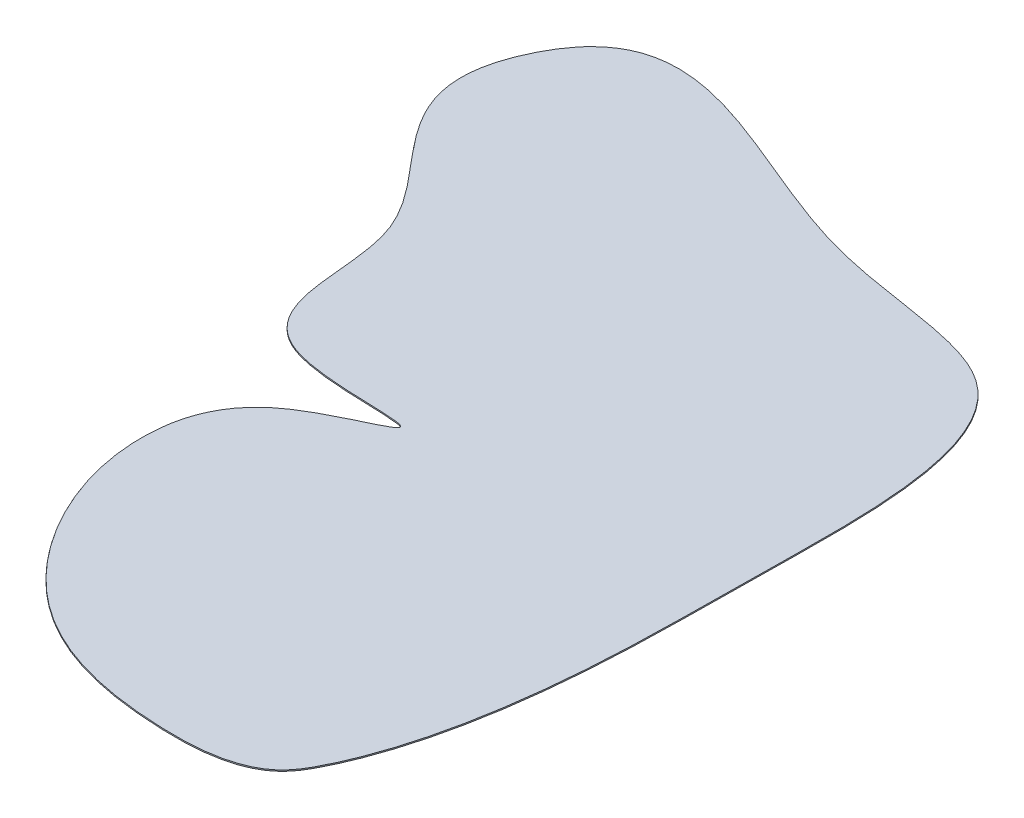
SolidWorks part; units mm, degrees
ref_plane "Front Plane" through (0, 0, 0) normal (0, 0, 1) x (1, 0, 0)
ref_plane "Top Plane" through (0, 0, 0) normal (0, 1, 0) x (1, 0, 0)
ref_plane "Right Plane" through (0, 0, 0) normal (1, 0, 0) x (0, 0, -1)
sketch "Sketch2" plane through (0, 0, 0) normal (0, 1, 0) x (1, 0, 0)
  line L1 (0, 0) -> (2743.2, 0)
  line L2 (0, 0) -> (0, -2743.2)
  line L3 (0, -2743.2) -> (2743.2, -2743.2)
  line L4 (2743.2, 0) -> (2743.2, -2743.2)
extrude "Boss-Extrude5" add sketch "Sketch2" along normal blind 2.54
sketch "Sketch4" plane through (0, 2.54, 0) normal (0, 1, 0) x (1, 0, 0)
  spline S0 degree 3 poles (912.5851, -1380.7074) (1381.1906, -1433.3821) (1879.5356, -1554.1962) (2340.6315, -1380.7074) knots 0 0 0 0 1 1 1 1
  spline S1 degree 3 poles (508.2148, -36.4494) (1278.1428, 110.5507) (1893.8971, -792.3816) (2340.6315, -1245.9173) knots 0 0 0 0 1 1 1 1
  spline S2 degree 2 poles (2340.6315, -1245.9173) (2450.1822, -1317.6681) (2340.6315, -1380.7074) knots 0 0 0 1 1 1
  spline S3 degree 2 poles (508.2148, -36.4494) (312.8785, -166.8791) (709.473, -780.8158) (756.1357, -1121.0937) (912.5851, -1380.7074) knots 0 0 0 0.294459 0.556343 1 1 1
  spline S4 degree 3 poles (1313.1183, -1433.2036) (1097.5204, -1463.953) (773.7784, -1944.1304) (1038.9673, -2482.472) (1775.7599, -2805.8672) (1973.2946, -2464.0408) (2375.0433, -2093.123) (2340.6315, -1380.7074) knots 0 0 0 0 0.213912 0.489653 0.685703 0.807002 1 1 1 1
sketch "Sketch5" plane through (0, 2.54, 0) normal (0, 1, 0) x (1, 0, 0)
  spline S0 degree 3 poles (1381.3756, -263.9505) (648.1941, 291.037) (273.3071, -491.0258) (878.115, -756.9647) (663.6876, -1474.9566) (1518.0338, -1382.9184) (985.0242, -1563.1188) (841.4333, -1982.3187) (1137.3701, -2567.7038) (1643.589, -2719.5859) (2078.1199, -2695.3967) (2253.6418, -2382.1782) (2342.36, -1856.4937) (2333.5656, -1207.2949) (2374.3537, -218.6699) (1381.3756, -263.9505) (648.1941, 291.037) (273.3071, -491.0258) knots -0.289077 -0.180775 -0.110557 0 0.021292 0.117399 0.193525 0.246711 0.285262 0.327734 0.420663 0.498327 0.542346 0.55612 0.63606 0.710923 0.819225 0.889443 1 1.021292 1.117399 1.193525 only from (508.2148, -36.4494) to (508.2148, -36.4494)
  spline S1 degree 2 poles (508.2148, -36.4494) (312.8785, -166.8791) (709.473, -780.8158) (756.1357, -1121.0937) (912.5851, -1380.7074) knots 0 0 0 0.294459 0.556343 1 1 1 construction
  point P2 (2140.5255, -325.6449)
  point P4 (1987.2629, -2488.1721)
  point P8 (1987.2629, -2488.1721)
  point P10 (0, 0)
  point P14 (1987.2629, -2488.1721)
  point P16 (1987.2629, -2488.1721)
  point P18 (1987.2629, -2488.1721)
  point P32 (2214.3821, -2593.0422)
  point P34 (0, 0)
  point P35 (0, 0)
  point P36 (2328.8599, -1836.0122)
  point P37 (2048.2048, -2541.3426)
  point P38 (2236.5391, -1817.548)
  point P39 (2151.604, -340.4162)
  point P40 (2144.2184, -336.7234)
extrude "Boss-Extrude6" add sketch "Sketch5" along normal blind 1.5875 and the other way blind 1.5875
extrude "Cut-Extrude1" cut sketch "Sketch5<2>" against normal through all flip side to cut
sketch "Sketch5<2>" plane through (0, 2.54, 0) normal (0, 1, 0) x (1, 0, 0) same geometry as "Sketch5"
sketch "Sketch7" plane through (0, 4.1275, 0) normal (0, 1, 0) x (1, 0, 0)
  line L0 (2343.1267, -1039.1073) -> (752.5972, -1039.1073) construction
  line L1 (402.8731, 71.8636) -> (2343.1267, 71.8636) construction
  line L2 (402.8731, 71.8636) -> (402.8731, -2701.1548) construction
  line L3 (402.8731, -2701.1548) -> (2343.1267, -2701.1548) construction
  line L4 (2343.1267, 71.8636) -> (2343.1267, -2701.1548) construction
  spline S0 degree 3 poles (1381.3756, -263.9505) (648.1941, 291.037) (273.3071, -491.0258) (878.115, -756.9647) (663.6876, -1474.9566) (1518.0338, -1382.9184) (985.0242, -1563.1188) (841.4333, -1982.3187) (1137.3701, -2567.7038) (1643.589, -2719.5859) (2078.1199, -2695.3967) (2253.6418, -2382.1782) (2342.36, -1856.4937) (2333.5656, -1207.2949) (2374.3537, -218.6699) (1381.3756, -263.9505) (648.1941, 291.037) (273.3071, -491.0258) knots -0.289077 -0.180775 -0.110557 0 0.021292 0.117399 0.193525 0.246711 0.285262 0.327734 0.420663 0.498327 0.542346 0.55612 0.63606 0.710923 0.819225 0.889443 1 1.021292 1.117399 1.193525 only from (508.2148, -36.4494) to (508.2148, -36.4494) construction
